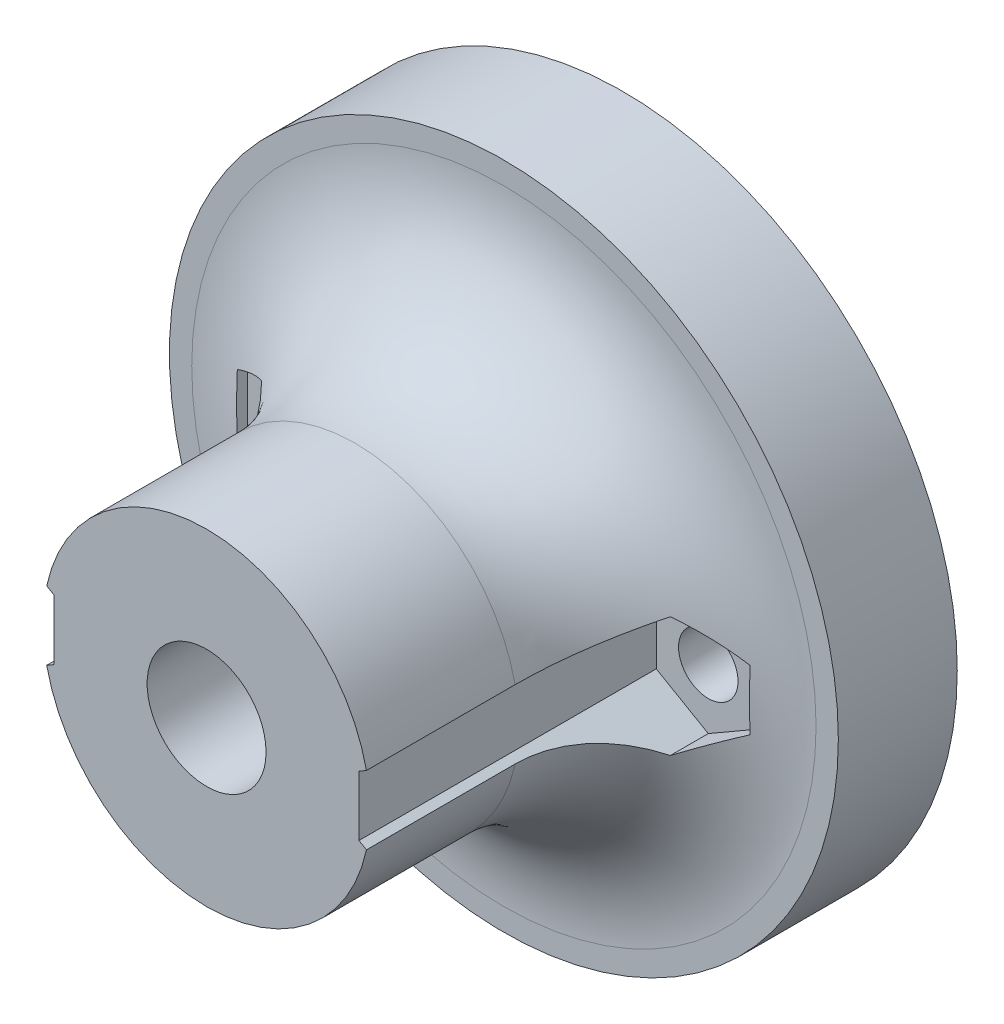
SolidWorks part; units mm, degrees
ref_plane "Front Plane" through (0, 0, 0) normal (0, 0, 1) x (1, 0, 0)
ref_plane "Top Plane" through (0, 0, 0) normal (0, 1, 0) x (1, 0, 0)
ref_plane "Right Plane" through (0, 0, 0) normal (1, 0, 0) x (0, 0, -1)
sketch "Sketch1" plane through (0, 0, 0) normal (0, 0, 1) x (1, 0, 0)
  line L1 (0, 9.815) -> (-8.5, 4.9075)
  line L2 (-8.5, 4.9075) -> (-8.5, -4.9075)
  line L3 (-8.5, -4.9075) -> (0, -9.815)
  line L4 (0, -9.815) -> (8.5, -4.9075)
  line L5 (8.5, -4.9075) -> (8.5, 4.9075)
  line L6 (8.5, 4.9075) -> (0, 9.815)
  circle A0 centre (0, 0) radius 22.5
  circle A1 centre (-13.75, 0) radius 2
  circle A2 centre (13.75, 0) radius 2
  circle A3 centre (0, 0) radius 8.5 construction
  point P7 (4.25, -7.3612)
  dimension "D2" = 4
  dimension "D5" = 4
  dimension "D6" = 45
  dimension "D1" = 17
  dimension "D3" = 13.75
  dimension "D4" = 13.75
extrude "Boss-Extrude1" add sketch "Sketch1" along normal blind 8
sketch "Sketch2" plane through (0, 0, 8) normal (0, 0, 1) x (1, 0, 0)
  circle A0 centre (0, 0) radius 11
  circle A1 centre (0, 0) radius 4
  dimension "D1" = 8
  dimension "D2" = 22
extrude "Boss-Extrude2" add sketch "Sketch2" along normal blind 20
fillet "Fillet1" radius 10 1 edges at (11, 0, 8)
sketch "Sketch3" plane through (0, 0, 0) normal (0, 0, -1) x (-1, 0, 0)
  line L1 (-13.75, 4.0415) -> (-17.25, 2.0207)
  line L2 (-17.25, 2.0207) -> (-17.25, -2.0207)
  line L3 (-17.25, -2.0207) -> (-13.75, -4.0415)
  line L4 (-13.75, -4.0415) -> (-10.25, -2.0207)
  line L5 (-10.25, -2.0207) -> (-10.25, 2.0207)
  line L6 (-10.25, 2.0207) -> (-13.75, 4.0415)
  line L7 (13.75, 4.0415) -> (10.25, 2.0207)
  line L8 (10.25, 2.0207) -> (10.25, -2.0207)
  line L9 (10.25, -2.0207) -> (13.75, -4.0415)
  line L10 (13.75, -4.0415) -> (17.25, -2.0207)
  line L11 (17.25, -2.0207) -> (17.25, 2.0207)
  line L12 (17.25, 2.0207) -> (13.75, 4.0415)
  circle A0 centre (-13.75, 0) radius 3.5 construction
  circle A1 centre (13.75, 0) radius 3.5 construction
  dimension "D1" = 7
  dimension "D2" = 7
extrude "Cut-Extrude1" cut sketch "Sketch3" against normal through all from offset 8 offset against normal yes
